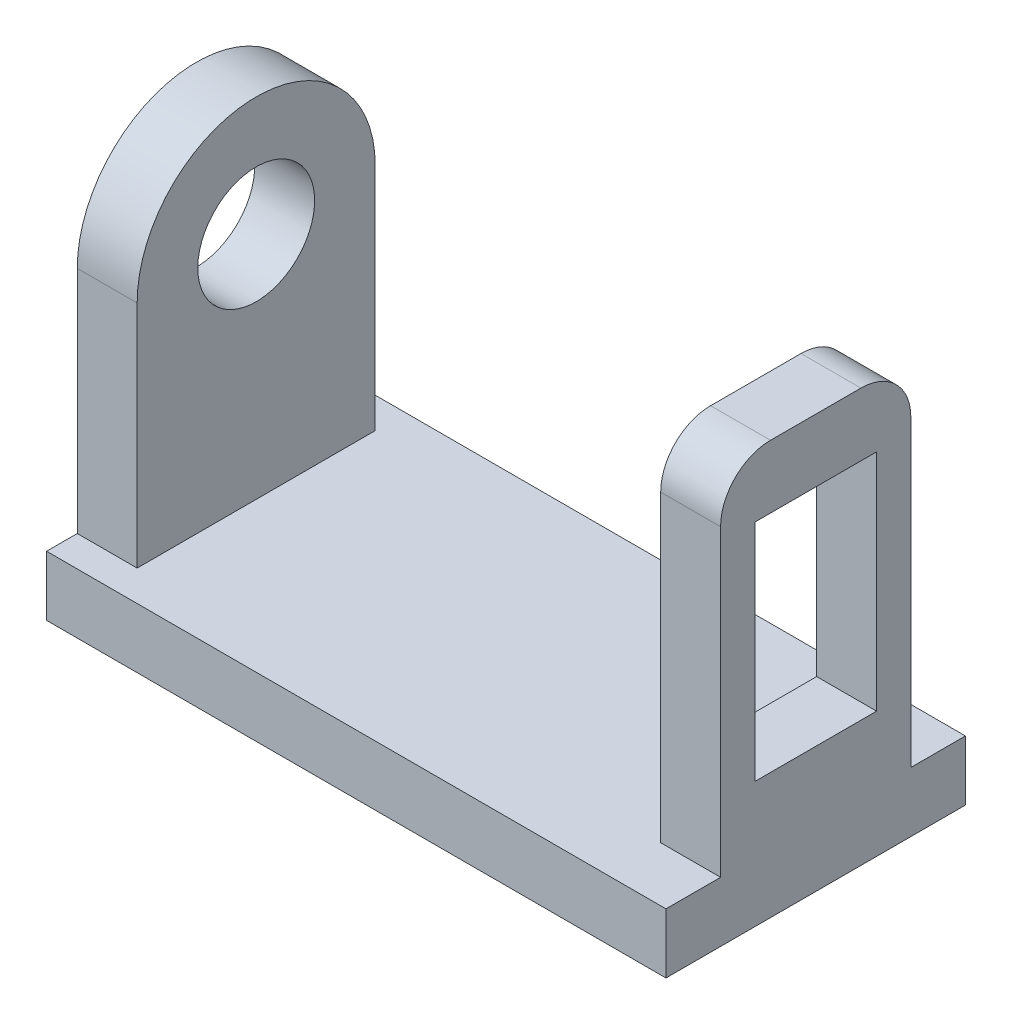
SolidWorks part; units mm, degrees
ref_plane "前视基准面" through (0, 0, 0) normal (0, 0, 1) x (1, 0, 0)
ref_plane "上视基准面" through (0, 0, 0) normal (0, 1, 0) x (1, 0, 0)
ref_plane "右视基准面" through (0, 0, 0) normal (1, 0, 0) x (0, 0, -1)
sketch "草图1" plane through (0, 0, 0) normal (0, 1, 0) x (1, 0, 0)
  line L0 (0, 0) -> (3.025, 0) construction
  line L1 (34.05, -15) -> (-28, -15)
  line L2 (34.05, -15) -> (34.05, 15)
  line L3 (34.05, 15) -> (-28, 15)
  line L4 (-28, -15) -> (-28, 15)
  line L5 (34.05, -15) -> (-28, 15) construction
  line L6 (34.05, 15) -> (-28, -15) construction
  point P0 (0, 0)
  dimension "D1" = 28
  dimension "D2" = 34.05
  dimension "D3" = 30
extrude "凸台-拉伸1" add sketch "草图1" along normal blind 6
sketch "草图2" plane through (-28, 0, 0) normal (-1, 0, 0) x (0, 0, 1)
  line L0 (-15, 6) -> (15, 6) construction
  line L1 (11.9252, 40.9252) -> (-11.9252, 40.9252)
  line L2 (11.9252, 40.9252) -> (11.9252, 6)
  line L3 (11.9252, 6) -> (-11.9252, 6)
  line L4 (-11.9252, 40.9252) -> (-11.9252, 6)
  line L5 (11.9252, 40.9252) -> (-11.9252, 6) construction
  line L6 (11.9252, 6) -> (-11.9252, 40.9252) construction
  line L7 (0, 23.4626) -> (0, 6) construction
  circle A0 centre (0, 29) radius 5.8528
  circle A1 centre (0, 29) radius 11.9252 construction
  point P0 (0, 23.4626)
  dimension "D1" = 23
extrude "凸台-拉伸2" add sketch "草图2" against normal blind 6
fillet "圆角1" 2 edges at (-25, 40.9252, -11.9252) (-25, 40.9252, 11.9252) type full round first side face at (-25, 23.4626, -11.9252) second side face at (-25, 23.4626, 11.9252) middle face at (-25, 40.9252, 0)
sketch "草图3" plane through (34.05, 0, 0) normal (1, 0, 0) x (0, 0, -1)
  line L1 (9.5285, 41.4153) -> (-9.5285, 41.4153)
  line L2 (9.5285, 41.4153) -> (9.5285, 6)
  line L3 (9.5285, 6) -> (-9.5285, 6)
  line L4 (-9.5285, 41.4153) -> (-9.5285, 6)
  line L5 (9.5285, 41.4153) -> (-9.5285, 6) construction
  line L6 (9.5285, 6) -> (-9.5285, 41.4153) construction
  line L7 (0, 23.85) -> (0, 0) construction
  line L8 (6.1, 35.1) -> (-6.1, 35.1)
  line L9 (6.1, 35.1) -> (6.1, 12.6)
  line L10 (6.1, 12.6) -> (-6.1, 12.6)
  line L11 (-6.1, 35.1) -> (-6.1, 12.6)
  line L12 (6.1, 35.1) -> (-6.1, 12.6) construction
  line L13 (6.1, 12.6) -> (-6.1, 35.1) construction
  line L17 (-15, 6) -> (15, 6) construction
  circle A0 centre (0, 29) radius 5.8528 construction
  circle A1 centre (0, 29) radius 5.8528 construction
  point P0 (0, 23.7076)
  point P7 (0, 23.85)
  dimension "D1" = 22.5
  dimension "D2" = 12.2
  dimension "D3" = 6.1
extrude "凸台-拉伸3" add sketch "草图3" against normal blind 6
fillet "圆角2" radius 5 2 edges at (31.05, 41.4153, 9.5285) (31.05, 41.4153, -9.5285)
